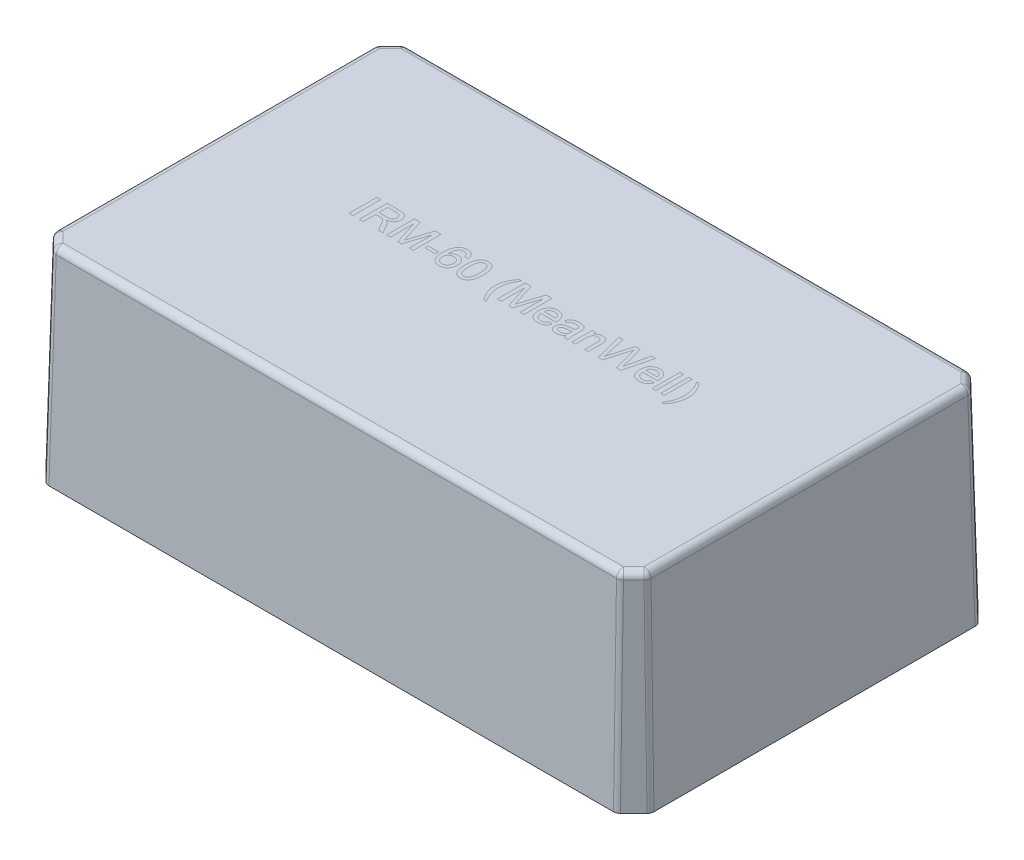
SolidWorks part; units mm, degrees
ref_plane "Спереди" through (0, 0, 0) normal (0, 0, 1) x (1, 0, 0)
ref_plane "Сверху" through (0, 0, 0) normal (0, 1, 0) x (1, 0, 0)
ref_plane "Справа" through (0, 0, 0) normal (1, 0, 0) x (0, 0, -1)
sketch "Эскиз1" plane through (0, 0, 0) normal (0, 1, 0) x (1, 0, 0)
  line L8 (0, 0) -> (110.8806, 0) construction
  line L9 (0, 0) -> (0, 62.4063) construction
  line L10 (-43.5, 23.5) -> (-41, 26)
  line L11 (-41, -26) -> (41, -26)
  line L12 (-43.5, -23.5) -> (-43.5, 23.5)
  line L13 (-41, 26) -> (41, 26)
  line L14 (43.5, -23.5) -> (43.5, 23.5)
  line L15 (41, 26) -> (43.5, 23.5)
  line L16 (41, -26) -> (43.5, -23.5)
  line L17 (-43.5, -23.5) -> (-41, -26)
  point P0 (0, 26)
  point P2 (-44.249, -23.8375)
  point P3 (-43.5, -26)
  point P4 (43.5, 26)
  point P5 (-43.5, 26)
  point P6 (43.5, -26)
  point P14 (-43.5, -23.8375)
  point P20 (0, 0)
  point P21 (-43.5, 0)
  dimension "D1" = 87
  dimension "D2" = 52
  dimension "D7" = 47
extrude "Бобышка-Вытянуть1" add sketch "Эскиз1" along normal blind 29.5 draft 1.5
fillet "Скругление1" radius 1 16 edges at (43.1138, 14.75, 23.34) (40.84, 14.75, 25.6138) (43.1138, 14.75, -23.34) (40.84, 14.75, -25.6138) (-40.84, 14.75, -25.6138) (-43.1138, 14.75, -23.34) (-41.7038, 29.5, -24.2038) (0, 29.5, -25.2275) (41.7038, 29.5, -24.2038) (42.7275, 29.5, 0) (41.7038, 29.5, 24.2038) (0, 29.5, 25.2275) (-42.7275, 29.5, 0) (-41.7038, 29.5, 24.2038) (-43.1138, 14.75, 23.34) (-40.84, 14.75, 25.6138)
sketch "Эскиз2" plane through (0, 0, 0) normal (0, -1, 0) x (1, 0, 0)
  line L0 (-37.8, -34.096) -> (-37.8, -50.5614) construction
  line L1 (-43.5, -23.0859) -> (-43.5, 23.0859) construction
  line L2 (-40.5859, 26) -> (40.5859, 26) construction
  line L3 (38.2, 4.1272) -> (38.2, -28.1589) construction
  line L4 (43.5, 23.0859) -> (43.5, -23.0859) construction
  circle A0 centre (-37.8, -14.75) radius 1
  circle A1 centre (-37.8, -20.25) radius 1
  circle A2 centre (38.2, 21) radius 0.5
  circle A3 centre (38.2, 14.25) radius 0.5
  dimension "D2" = 40.75
  dimension "D5" = 5
  dimension "D1" = 5.7
  dimension "D3" = 5.5
  dimension "D4" = 76
  dimension "D6" = 6.75
extrude "Бобышка-Вытянуть2" add sketch "Эскиз2" along normal blind 3.5
fillet "Скругление2" radius 0.25 4 edges at (38.2, -3.5, 20.5) (38.2, -3.5, 13.75) (-37.8, -3.5, -15.75) (-37.8, -3.5, -21.25)
sketch "Эскиз3" plane through (0, 29.5, 0) normal (0, 1, 0) x (1, 0, 0)
  text T0 "IRM-60 (MeanWell)"
wrap "Перенос1" sketch "Эскиз3" wrap type scribe source sketch "Эскиз3" face at (0, 29.5, 0)
